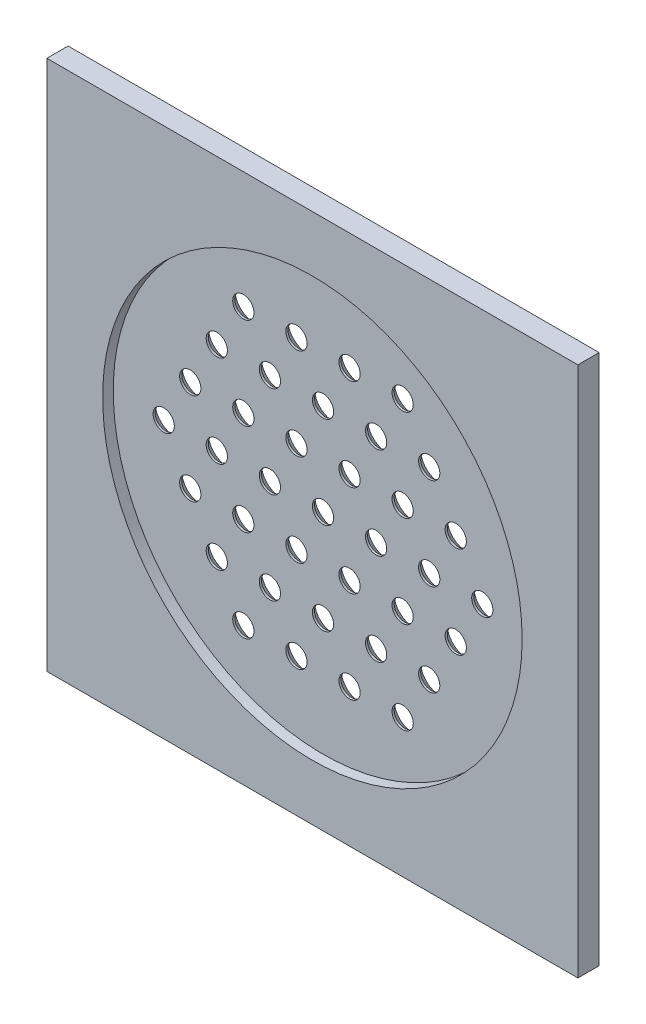
SolidWorks part; units mm, degrees
material "Сосна"
ref_plane "Front" through (0, 0, 0) normal (0, 0, 1) x (1, 0, 0)
ref_plane "Top" through (0, 0, 0) normal (0, 1, 0) x (1, 0, 0)
ref_plane "Right" through (0, 0, 0) normal (1, 0, 0) x (0, 0, -1)
sketch "Эскиз1" plane through (0, 66.7543, 0) normal (0, 0, 1) x (-1, 0, 0)
  line L36 (0, 66.7543) -> (50, 66.7543)
  line L37 (0, 66.7543) -> (0, 16.7543)
  line L38 (0, 16.7543) -> (50, 16.7543)
  line L39 (50, 66.7543) -> (50, 16.7543)
  dimension "D1" = 50
  dimension "D2" = 50
extrude "Бобышка-Вытянуть1" add sketch "Эскиз1" along normal blind 2
sketch "Эскиз2" plane through (0, 0, 2) normal (0, 0, 1) x (1, 0, 0)
  line L0 (-20, 16.3397) -> (-30, 16.3397) construction
  line L1 (-32.5, 12.0096) -> (-27.5, 12.0096) construction
  line L2 (-27.5, 12.0096) -> (-22.5, 12.0096) construction
  line L4 (-17.5, 12.0096) -> (-22.5, 12.0096) construction
  circle A1 centre (-25, 25) radius 1
  circle A2 centre (-20, 25) radius 1
  circle A3 centre (-15, 25) radius 1
  circle A4 centre (-10, 25) radius 1
  circle A5 centre (-22.5, 20.6699) radius 1
  circle A6 centre (-20, 16.3397) radius 1
  circle A7 centre (-17.5, 12.0096) radius 1
  circle A8 centre (-27.5, 20.6699) radius 1
  circle A9 centre (-30, 16.3397) radius 1
  circle A10 centre (-32.5, 12.0096) radius 1
  circle A11 centre (-30, 25) radius 1
  circle A12 centre (-35, 25) radius 1
  circle A13 centre (-40, 25) radius 1
  circle A14 centre (-27.5, 29.3301) radius 1
  circle A15 centre (-30, 33.6603) radius 1
  circle A16 centre (-32.5, 37.9904) radius 1
  circle A17 centre (-22.5, 29.3301) radius 1
  circle A18 centre (-20, 33.6603) radius 1
  circle A19 centre (-17.5, 37.9904) radius 1
  circle A20 centre (-25, 16.3397) radius 1
  circle A21 centre (-27.5, 12.0096) radius 1
  circle A22 centre (-22.5, 12.0096) radius 1
  circle A23 centre (-32.5, 20.6699) radius 1
  circle A24 centre (-37.5, 20.6699) radius 1
  circle A25 centre (-35, 16.3397) radius 1
  circle A26 centre (-32.5, 29.3301) radius 1
  circle A27 centre (-35, 33.6603) radius 1
  circle A28 centre (-37.5, 29.3301) radius 1
  circle A29 centre (-25, 33.6603) radius 1
  circle A30 centre (-22.5, 37.9904) radius 1
  circle A31 centre (-27.5, 37.9904) radius 1
  circle A32 centre (-17.5, 29.3301) radius 1
  circle A33 centre (-12.5, 29.3301) radius 1
  circle A34 centre (-15, 33.6603) radius 1
  circle A35 centre (-17.5, 20.6699) radius 1
  circle A36 centre (-15, 16.3397) radius 1
  circle A37 centre (-12.5, 20.6699) radius 1
  point P42 (-25, 25)
  point P80 (-25, 25)
  point P92 (-25, 16.3397)
  dimension "D1" = 4
  dimension "D6" = 2
  dimension "D3" = 3
  dimension "D7" = 25
  dimension "D8" = 25
  dimension "D9" = 10
  dimension "D4" = 2
  dimension "D2" = 6
  dimension "D5" = 6
extrude "Отверстия для динамика" cut sketch "Эскиз2" against normal through all
sketch "Эскиз3" plane through (0, 0, 2) normal (0, 0, 1) x (1, 0, 0)
  circle A0 centre (-25, 25) radius 19.75
  dimension "D1" = 39.5
extrude "Вырез под динамик" cut sketch "Эскиз3" against normal blind 1
chamfer "Фаска1" distance 0.8 angle 45 37 edges at (-14, 16.3397, 0) (-9, 25, 0) (-11.5, 20.6699, 0) (-16.5, 12.0096, 0) (-21.5, 12.0096, 0) (-19, 16.3397, 0) (-16.5, 20.6699, 0) (-14, 25, 0) (-11.5, 29.3301, 0) (-14, 33.6603, 0) (-16.5, 29.3301, 0) (-19, 25, 0) (-21.5, 20.6699, 0) (-26.5, 12.0096, 0) (-24, 16.3397, 0) (-26.5, 20.6699, 0) (-31.5, 12.0096, 0) (-29, 16.3397, 0) (-34, 16.3397, 0) (-31.5, 20.6699, 0) (-36.5, 20.6699, 0) (-19, 33.6603, 0) (-21.5, 29.3301, 0) (-24, 25, 0) (-26.5, 29.3301, 0) (-29, 25, 0) (-31.5, 29.3301, 0) (-34, 25, 0) (-39, 25, 0) (-36.5, 29.3301, 0) (-29, 33.6603, 0) (-34, 33.6603, 0) (-31.5, 37.9904, 0) (-26.5, 37.9904, 0) (-24, 33.6603, 0) (-21.5, 37.9904, 0) (-16.5, 37.9904, 0)
